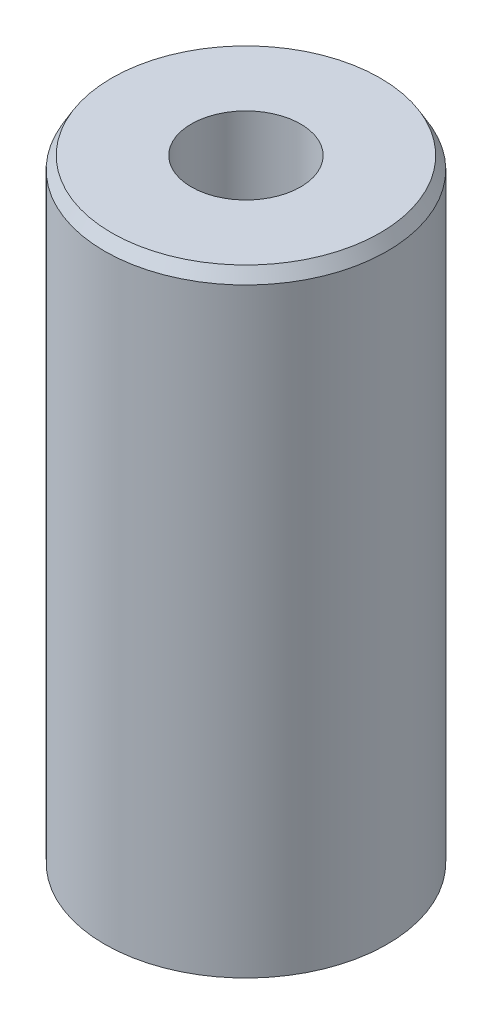
SolidWorks part; units mm, degrees
ref_plane "Front Plane" through (0, 0, 0) normal (0, 0, 1) x (1, 0, 0)
ref_plane "Top Plane" through (0, 0, 0) normal (0, 1, 0) x (1, 0, 0)
ref_plane "Right Plane" through (0, 0, 0) normal (1, 0, 0) x (0, 0, -1)
sketch "Sketch1" plane through (0, 0, 0) normal (0, 1, 0) x (1, 0, 0)
  circle A0 centre (0, 0) radius 37.5
  dimension "SHAFT_OD" = 75
extrude "Boss-Extrude1" add sketch "Sketch1" along normal blind 164.4342
sketch "Sketch2" plane through (0, 0, 0) normal (0, 1, 0) x (1, 0, 0)
  circle A0 centre (0, 0) radius 14.4948
  dimension "BORE_D" = 28.9896
extrude "Cut-Extrude1" cut sketch "Sketch2" along normal through all
chamfer "Chamfer1" distance 3.2618 angle 30 2 edges at (0, 164.4342, 37.5) (0, 0, 37.5) first distance on face at (0, 164.4342, 37.5) first distance on face at (0, 0, 14.4948)
